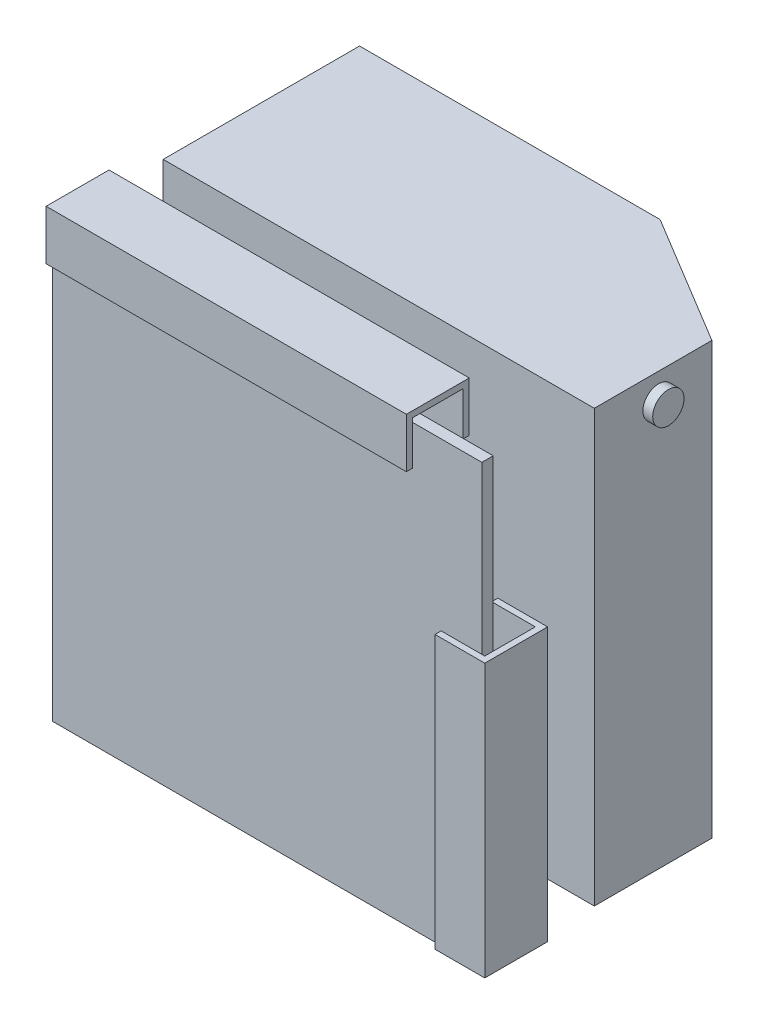
SolidWorks part; units mm, degrees
ref_plane "Front Plane" through (0, 0, 0) normal (0, 0, 1) x (1, 0, 0)
ref_plane "Top Plane" through (0, 0, 0) normal (0, 1, 0) x (1, 0, 0)
ref_plane "Right Plane" through (0, 0, 0) normal (1, 0, 0) x (0, 0, -1)
ref_plane "PY -55.000" through (0, -55, 0) normal (0, 1, 0) x (1, 0, 0)
sketch "housing sketch" plane through (0, -55, 0) normal (0, 1, 0) x (1, 0, 0)
  line L0 (0, 0) -> (0, 30)
  line L1 (0, 30) -> (-33.3047, 50.1)
  line L2 (-33.3047, 50.1) -> (-110, 50.1)
  line L3 (-110, 50.1) -> (-110, 0)
  line L4 (-110, 0) -> (0, 0)
extrude "housing" add sketch "housing sketch" along normal mid plane 110
ref_plane "PZ 26.850" through (0, 0, 26.85) normal (0, 0, 1) x (1, 0, 0)
sketch "diffuser sketch" plane through (0, 0, 26.85) normal (0, 0, 1) x (1, 0, 0)
  line L0 (-110, -110) -> (-0.4, -110)
  line L1 (-0.4, -110) -> (-0.4, 2)
  line L2 (-0.4, 2) -> (-110, 2)
  line L3 (-110, 2) -> (-110, -110)
extrude "diffuser" add sketch "diffuser sketch" along normal mid plane 2.9
ref_plane "PY -75.215" through (0, -75.215, 0) normal (0, 1, 0) x (1, 0, 0)
sketch "side channel sketch" plane through (0, -75.215, 0) normal (0, 1, 0) x (1, 0, 0)
  line L0 (-10.78, -13.83) -> (1.92, -13.83)
  line L1 (1.92, -13.83) -> (1.92, -29.87)
  line L2 (1.92, -29.87) -> (-10.78, -29.87)
  line L3 (-10.78, -29.87) -> (-10.78, -28.3)
  line L4 (-10.78, -28.3) -> (0.35, -28.3)
  line L5 (0.35, -28.3) -> (0.35, -15.4)
  line L6 (0.35, -15.4) -> (-10.78, -15.4)
  line L7 (-10.78, -15.4) -> (-10.78, -13.83)
extrude "side channel" add sketch "side channel sketch" along normal mid plane 69.57
ref_plane "PX -64.040" through (-64.04, 0, 0) normal (1, 0, 0) x (0, 0, -1)
sketch "end channel sketch" plane through (-64.04, 0, 0) normal (1, 0, 0) x (0, 0, -1)
  line L0 (-13.83, -8.13) -> (-13.83, 4.57)
  line L1 (-13.83, 4.57) -> (-29.87, 4.57)
  line L2 (-29.87, 4.57) -> (-29.87, -8.13)
  line L3 (-29.87, -8.13) -> (-28.3, -8.13)
  line L4 (-28.3, -8.13) -> (-28.3, 3)
  line L5 (-28.3, 3) -> (-15.4, 3)
  line L6 (-15.4, 3) -> (-15.4, -8.13)
  line L7 (-15.4, -8.13) -> (-13.83, -8.13)
extrude "end channel" add sketch "end channel sketch" along normal mid plane 91.92
ref_plane "PX 0.750" through (0.75, 0, 0) normal (1, 0, 0) x (0, 0, -1)
sketch "side screw head sketch" plane through (0.75, 0, 0) normal (1, 0, 0) x (0, 0, -1)
  circle A0 centre (16.4, -6.8) radius 4
extrude "side screw head" add sketch "side screw head sketch" along normal mid plane 3.5
ref_plane "PY -20.700" through (0, -20.7, 0) normal (0, 1, 0) x (1, 0, 0)
sketch "insert flange sketch" plane through (0, -20.7, 0) normal (0, 1, 0) x (1, 0, 0)
  line L0 (-18.3249, 39.8914) -> (-17.2914, 41.6037)
  line L1 (-17.2914, 41.6037) -> (-12.026, 38.426)
  line L2 (-12.026, 38.426) -> (-13.0595, 36.7136)
  line L3 (-13.0595, 36.7136) -> (-18.3249, 39.8914)
revolve "insert flange" add sketch "insert flange sketch" angle 360 about L0
equation "\"diffL\" = 608.8mm"
equation "\"diffW\" = 329.4mm"
equation "\"diffT\" = 2.9mm"
equation "\"chanSlotW\" = 12.9mm"
equation "\"chanSlotDepth\" = 11.13mm"
equation "\"chanFloor\" = 1.57mm"
equation "\"chanLeg\" = 12.7mm"
equation "\"lightL\" = 605mm"
equation "\"lightW\" = 331mm"
equation "\"lightH\" = 92mm"
equation "\"lightSideFlat\" = 30mm"
equation "\"lightSlopeLen\" = 33.1mm"
equation "\"lightWingDepth\" = 47.9mm"
equation "\"lightWingFlat\" = 90.2mm"
equation "\"lightChanW\" = 99.6mm"
equation "\"lightChanStand\" = 44.1mm"
equation "\"insFlangeD\" = 12.3mm"
equation "\"insFromEnd\" = 20.7mm"
equation "\"insUpSlope\" = 20.8mm"
equation "\"gaugeH\" = 10mm"
equation "\"gaugeStepLen\" = 14mm"
equation "\"gaugeStepW0\" = 13.1mm"
equation "\"gaugeStepDW\" = 0.2mm"
equation "\"gaugeSteps\" = 5mm"
equation "\"gaugeHandleLen\" = 30mm"
equation "\"gaugeHandleW\" = 24mm"
equation "\"gaugeSlot0\" = 3mm"
equation "\"gaugeSlotD\" = 0.1mm"
equation "\"gaugeSlotDepth\" = 8mm"
equation "\"gap\" = 25.4mm"
equation "\"edgeL\" = 1mm"
equation "\"edgeW\" = 0.75mm"
equation "\"proud\" = 1.5mm"
equation "\"seatClr\" = 0.15mm"
equation "\"tongueClrZ\" = 0.1mm"
equation "\"tongueClrX\" = 0.25mm"
equation "\"tongueLen\" = 30mm"
equation "\"armSide\" = 45mm"
equation "\"armEnd\" = 20mm"
equation "\"cornerCham\" = 3mm"
equation "\"brkW\" = 26mm"
equation "\"brkT\" = 7mm"
equation "\"brkSeatClr\" = 0.2mm"
equation "\"brkScrewSpan\" = 16mm"
equation "\"pilotD\" = 2.7mm"
equation "\"pilotDepth\" = 10mm"
equation "\"screwClrD\" = 3.9mm"
equation "\"jogBelow\" = 4mm"
equation "\"padT\" = 7mm"
equation "\"padLen\" = 31mm"
equation "\"m6Clr\" = 7mm"
equation "\"m6Slot\" = 3mm"
equation "\"flangeRelD\" = 17mm"
equation "\"flangeRelDepth\" = 1.5mm"
equation "\"relLen\" = 7mm"
equation "\"relDepth\" = 4mm"
equation "\"relLand\" = 2mm"
equation "\"knockN\" = 100mm"
equation "\"petgcfE\" = 3000mm"
equation "\"mockExtent\" = 110mm"
equation "\"relZnear\" = 9.4mm"
equation "\"relZfar\" = 23.4mm"
equation "\"headD\" = 8mm"
equation "\"headH\" = 2.5mm"
equation "\"headFromEnd\" = 6.8mm"
equation "\"headBack\" = 16.4mm"
equation "\"sideClr\" = 0.4mm"
equation "\"cornerRelR\" = 1.5mm"
equation "\"cornerRelBack\" = 0.6mm"
equation "\"endHeadH\" = 2.8mm"
equation "\"footClr\" = 1.2mm"
equation "\"footEndClr\" = 3.5mm"
equation "\"footLift\" = 6mm"
equation "\"footBlockClr\" = 0.5mm"
equation "\"footBack\" = 50mm"
equation "\"footFwd\" = 10mm"
equation "\"footBraceEnd\" = 3mm"
equation "\"footLoadN\" = 25mm"
equation "\"spacerLen\" = 60mm"
equation "\"spacerShort\" = 0.5mm"
equation "\"spacerCham\" = 0.8mm"
equation "\"spacerPerSide\" = 3mm"
equation "\"spacerPerEnd\" = 1mm"
equation "\"toolR\" = 9mm"
equation "\"visR\" = 4mm"
equation "\"edgeR\" = 1mm"
equation "\"bendOutR\" = 5mm"
equation "\"insideR\" = 2.5mm"
equation "\"footCornerR\" = 10mm"
equation "\"footFrontR\" = 8mm"
equation "\"braceKinkR\" = 12mm"
equation "\"bedCham\" = 1mm"
equation "\"bedChamSmall\" = 0.6mm"
equation "\"soleTopR\" = 2mm"
equation "\"cornerR\" = 6mm"
equation "\"rimInR\" = 1mm"
equation "\"insFlangeH\" = 1mm"
